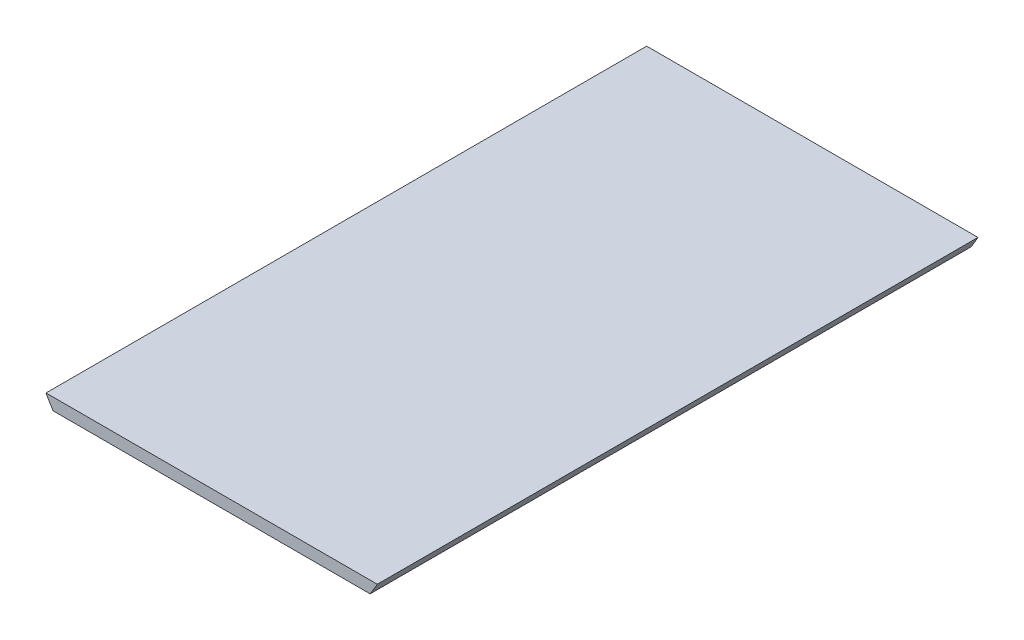
SolidWorks part; units mm, degrees
ref_plane "Front Plane" through (0, 0, 0) normal (0, 0, 1) x (1, 0, 0)
ref_plane "Top Plane" through (0, 0, 0) normal (0, 1, 0) x (1, 0, 0)
ref_plane "Right Plane" through (0, 0, 0) normal (1, 0, 0) x (0, 0, -1)
sketch "Sketch2" plane through (0, 0, 0) normal (0, 0, 1) x (1, 0, 0)
  line L0 (0, -24.5934) -> (0, -27.7938) construction
  line L2 (-44.45, -24.5934) -> (44.45, -24.5934)
  line L3 (42.5223, -27.7938) -> (-42.5223, -27.7938)
  arc A0 (42.5223, -27.7938) -> (44.45, -24.5934) centre (0, 0) ccw
  arc A2 (-44.45, -24.5934) -> (-42.5223, -27.7938) centre (0, 0) ccw
  dimension "D1" = 3.2004
extrude "Boss-Extrude1" add sketch "Sketch2" along normal blind 161.1884 contours L2 A0 L3 A2
